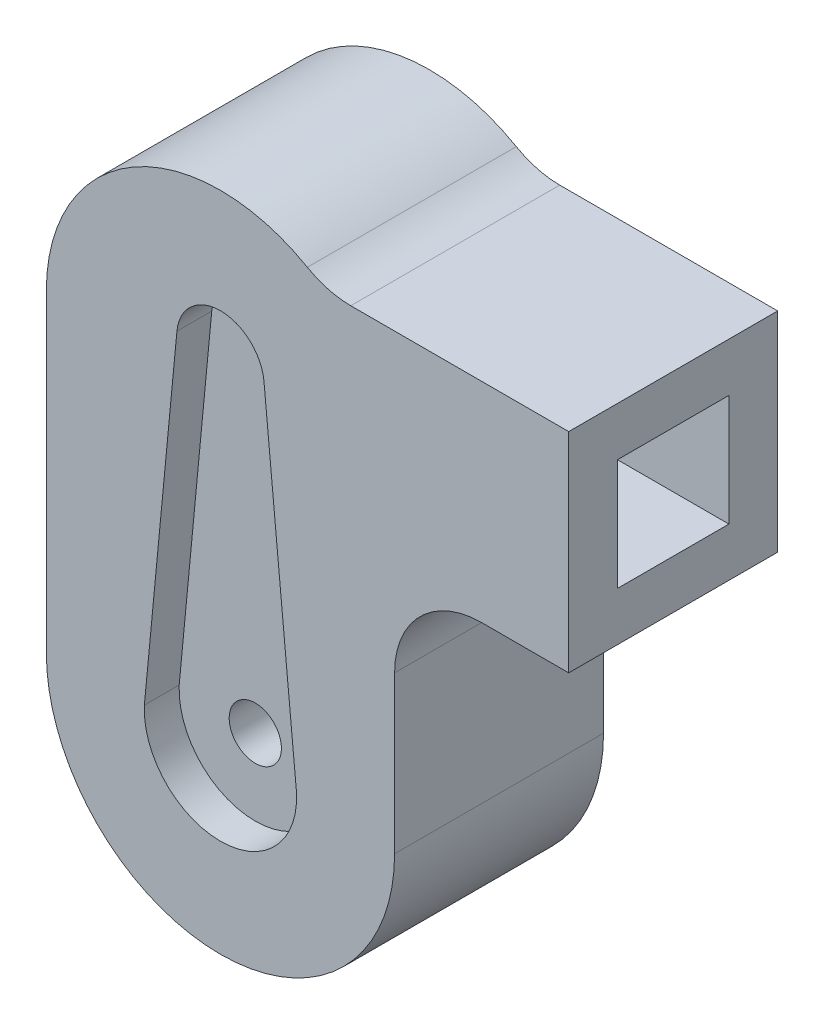
SolidWorks part; units mm, degrees
material "ABS"
ref_plane "Front Plane" through (0, 0, 0) normal (0, 0, 1) x (1, 0, 0)
ref_plane "Top Plane" through (0, 0, 0) normal (0, 1, 0) x (1, 0, 0)
ref_plane "Right Plane" through (0, 0, 0) normal (1, 0, 0) x (0, 0, -1)
sketch "Sketch1" plane through (0, 0, 0) normal (0, 0, 1) x (1, 0, 0)
  line L0 (0, 18) -> (0, 0) construction
  line L1 (10, 18) -> (10, 0)
  line L2 (-10, 18) -> (-10, 0)
  arc A1 (10, 18) -> (-10, 18) centre (0, 18) ccw
  arc A2 (-10, 0) -> (10, 0) centre (0, 0) ccw
  point P3 (0, 9)
  point P9 (0, 28)
  point P10 (0, -10)
  dimension "D1" = 20
  dimension "D2" = 38
sketch "Sketch2" plane through (0, 0, 0) normal (0, 0, 1) x (1, 0, 0)
  line L0 (0, 0) -> (0, 28) construction
  line L1 (-2.5, 19.7394) -> (-4.37, 0.2091)
  line L2 (2.5, 19.7394) -> (4.37, 0.2091)
  line L3 (-10, 0) -> (10, 0) construction
  line L8 (-10, 18) -> (-10, 0) construction
  line L9 (10, 18) -> (10, 0) construction
  arc A0 (-4.37, 0.2091) -> (4.37, -0.2091) centre (0, 0) ccw
  arc A2 (-2.5, 19.7394) -> (2.5, 19.7394) centre (0, 19.5) cw
  arc A3 (4.37, -0.2091) -> (4.37, 0.2091) centre (0, 0) ccw
  arc A5 (10, 18) -> (-10, 18) centre (0, 18) ccw construction
  dimension "D1" = 4.375
  dimension "D2" = 8.74
  dimension "D3" = 19.5
  dimension "D4" = 5
extrude "Boss-Extrude1" add sketch "Sketch1" against normal blind 12
sketch "Sketch4" plane through (0, 0, 0) normal (0, 0, 1) x (1, 0, 0)
  circle A0 centre (0, 0) radius 1.5
  dimension "D1" = 3
extrude "Cut-Extrude2" cut sketch "Sketch4" against normal through all
sketch "Sketch7" plane through (0, 0, 0) normal (1, 0, 0) x (0, 0, -1)
  line L0 (12, 18) -> (12, 28) construction
  line L1 (0, 26) -> (12, 26)
  line L2 (0, 26) -> (0, 14)
  line L3 (0, 14) -> (12, 14)
  line L4 (12, 26) -> (12, 14)
  point P7 (0, 20)
  point P9 (0, 0)
  dimension "D1" = 20
extrude "Boss-Extrude2" add sketch "Sketch7" along normal blind 20
extrude "Cut-Extrude1" cut sketch "Sketch2" against normal blind 2
ref_plane "Plane1" through (0, 5, 0) normal (0, 1, 0) x (1, 0, 0)
ref_axis "Axis1" through (0, 0, -12) along (0, 0, 1)
ref_plane "Plane2" through (0, 0, -6) normal (0, 0, 1) x (1, 0, 0)
mirror "Mirror1" about plane through (0, 0, -6) normal (0, 0, 1) of "Cut-Extrude1"
sketch "Sketch8" plane through (20, 0, 0) normal (1, 0, 0) x (0, 0, -1)
  line L0 (12, 26) -> (0, 26) construction
  line L1 (2.8, 23.2) -> (9.2, 23.2)
  line L2 (2.8, 23.2) -> (2.8, 16.8)
  line L3 (2.8, 16.8) -> (9.2, 16.8)
  line L4 (9.2, 23.2) -> (9.2, 16.8)
  line L5 (2.8, 23.2) -> (9.2, 16.8) construction
  line L6 (2.8, 16.8) -> (9.2, 23.2) construction
  line L7 (0, 20) -> (12, 20) construction
  line L8 (0, 26) -> (0, 14) construction
  line L9 (12, 14) -> (12, 26) construction
  line L10 (6, 26) -> (6, 14) construction
  line L11 (0, 14) -> (12, 14) construction
  point P0 (6, 20)
  point P18 (6, 20)
  dimension "D1" = 6.4
extrude "Cut-Extrude4" cut sketch "Sketch8" against normal up to surface (20 mm away) up to plane "Right Plane"
fillet "Fillet1" radius 5 2 edges at (10, 14, -6) (6, 26, -6)
